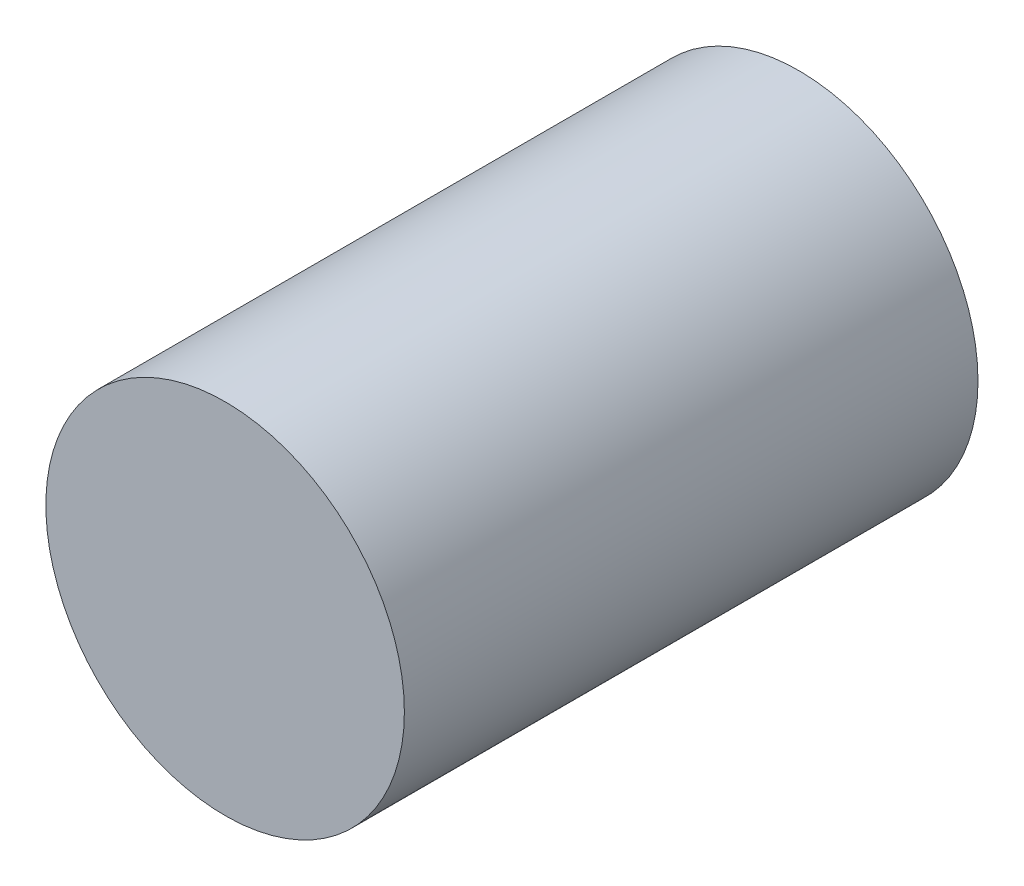
SolidWorks part; units mm, degrees
ref_plane "Front Plane" through (0, 0, 0) normal (0, 0, 1) x (1, 0, 0)
ref_plane "Top Plane" through (0, 0, 0) normal (0, 1, 0) x (1, 0, 0)
ref_plane "Right Plane" through (0, 0, 0) normal (1, 0, 0) x (0, 0, -1)
sketch "Sketch2" plane through (0, 0, 0) normal (0, 0, 1) x (1, 0, 0)
  circle A4 centre (0, 0) radius 2.5
  point P3 (25, 0)
ref_plane "Plane1" through (0, 0, 8) normal (0, 0, 1) x (1, 0, 0)
sketch "Sketch3" plane through (0, 0, 8) normal (0, 0, 1) x (1, 0, 0)
  circle A0 centre (0, 0) radius 2.5
loft "Loft1" add profiles "Sketch2", "Sketch3" connector at (0.2181, 2.4905, 0) connector at (0.0833, 2.4986, 8)
